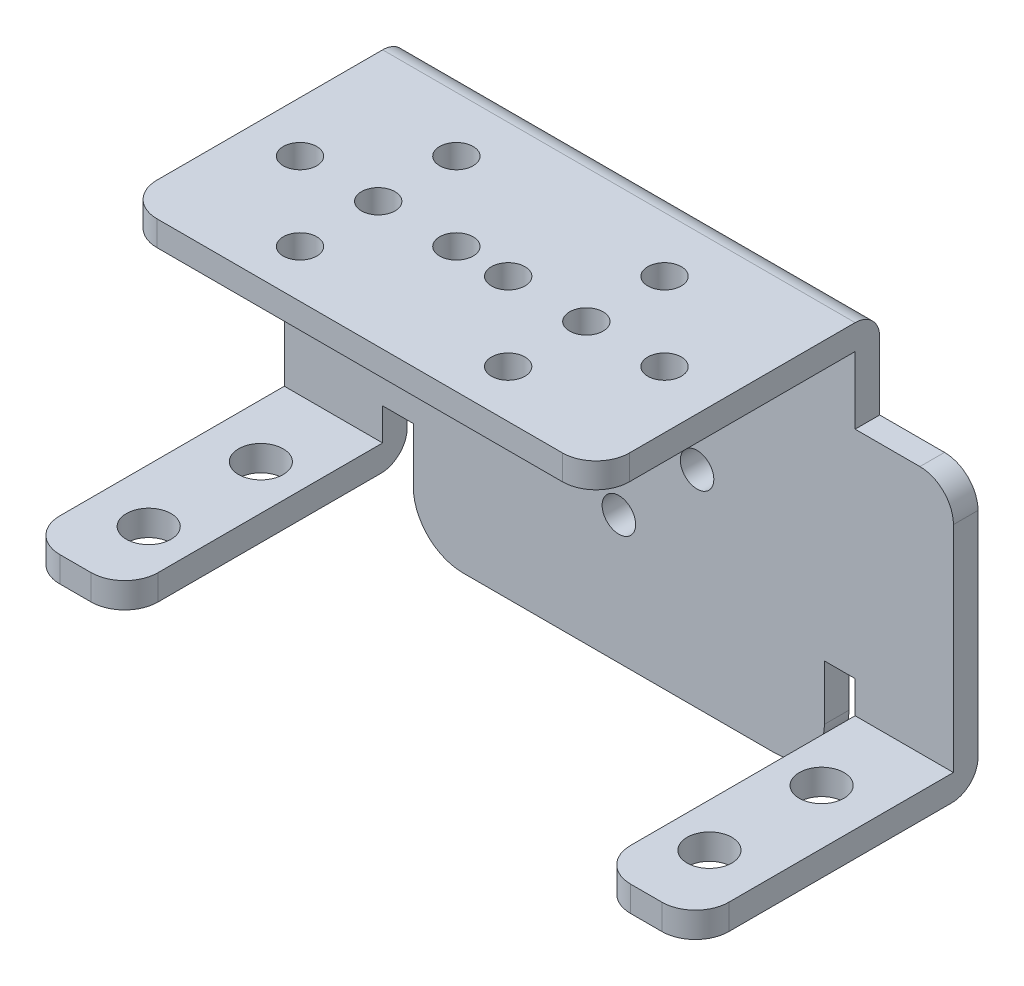
SolidWorks part; units mm, degrees
note: The reader was unsure of these and kept them because the rebuilt part matched: shared geometry of "Sketch1<3>", "Sketch1<4>".
ref_plane "前视基准面" through (0, 0, 0) normal (0, 0, 1) x (1, 0, 0)
ref_plane "上视基准面" through (0, 0, 0) normal (0, 1, 0) x (1, 0, 0)
ref_plane "右视基准面" through (0, 0, 0) normal (1, 0, 0) x (0, 0, -1)
sketch "Sketch1" plane through (0, 0, 0) normal (0, 0, 1) x (1, 0, 0)
  line L0 (-21.15, 16.24) -> (21.15, 16.24)
  line L1 (-21.15, 18.48) -> (21.15, 18.48)
  line L2 (-21.15, 18.48) -> (-21.15, -14.28)
  line L3 (-4.3498, -18.48) -> (13.96, -18.48)
  line L4 (21.15, 18.48) -> (21.15, -14.28)
  line L5 (-13.96, -18.48) -> (-4.3498, -18.48)
  line L6 (-18.4, -9.12) -> (18.4, -9.12)
  line L7 (-18.4, -9.12) -> (-18.4, -14.04)
  line L8 (-13.96, -18.48) -> (13.96, -18.48)
  line L9 (18.4, -9.12) -> (18.4, -14.04)
  line L10 (-4.3498, -18.48) -> (13.96, -18.48)
  line L11 (18.4, -9.12) -> (21.15, -9.12)
  line L12 (21.15, 10.22) -> (29.95, 10.22)
  line L13 (21.15, 10.22) -> (21.15, -14.28)
  line L14 (21.15, -14.28) -> (29.95, -14.28)
  line L15 (29.95, 10.22) -> (29.95, -14.28)
  line L16 (-29.95, 10.22) -> (-21.15, 10.22)
  line L17 (-29.95, 10.22) -> (-29.95, -14.28)
  line L18 (-29.95, -14.28) -> (-21.15, -14.28)
  line L19 (-21.15, 10.22) -> (-21.15, -14.28)
  line L20 (18.4, -9.12) -> (21.15, -9.12)
  line L21 (18.4, -9.12) -> (21.15, -9.12)
  line L22 (-18.4, -9.12) -> (-21.15, -9.12)
  line L24 (21.15, -12) -> (29.95, -12)
  line L25 (21.15, -12) -> (21.15, -14.28)
  line L26 (21.15, -14.28) -> (29.95, -14.28)
  line L27 (29.95, -12) -> (29.95, -14.28)
  line L28 (-29.95, -12) -> (-21.15, -12)
  line L29 (-29.95, -12) -> (-29.95, -14.28)
  line L30 (-29.95, -14.28) -> (-21.15, -14.28)
  line L31 (-21.15, -12) -> (-21.15, -14.28)
  arc A0 (-13.96, -18.48) -> (-18.4, -14.04) centre (-13.96, -14.04) cw
  arc A1 (13.96, -18.48) -> (18.4, -14.04) centre (13.96, -14.04) ccw
  point P20 (18.4, -18.48)
  point P30 (-25.55, -14.28)
  point P32 (-25.55, -12)
  dimension "D9" = 4.44
  dimension "D10" = 4.44
  dimension "D2" = 42.3
  dimension "D3" = 21.15
  dimension "D4" = 18.48
  dimension "D5" = 2.24
  dimension "D6" = 9.36
  dimension "D7" = 36.8
  dimension "D8" = 18.4
  dimension "D11" = 18.48
  dimension "D12" = 24.5
  dimension "D13" = 24.5
  dimension "D14" = 8.8
  dimension "D15" = 8.8
  dimension "D16" = 32.76
  dimension "D17" = 32.76
  dimension "D18" = 2.28
  dimension "D19" = 2.28
extrude "Boss-Extrude1" add sketch "Sketch1" along normal blind 2.2 contours L22 L6 L11 L4 L0 L2 | L3 A1 L9 L6 L7 A0 L5 | L17 L28 L19 L2 L16 | L4 L24 L15 L12
extrude "Boss-Extrude2" add sketch "Sketch1<3>" along normal blind 25.4 contours L4 L1 L2 L0
sketch "Sketch1<3>" plane through (0, 0, 0) normal (0, 0, 1) x (1, 0, 0) same geometry as "Sketch1"
extrude "Boss-Extrude3" add sketch "Sketch1<4>" along normal blind 25.3 contours L28 L17 L18 L2 | L24 L13 L14 L15
sketch "Sketch1<4>" plane through (0, 0, 0) normal (0, 0, 1) x (1, 0, 0) same geometry as "Sketch1"
fillet "Fillet13" radius 3 1 edges at (-21.15, -13.14, 25.3)
fillet "Fillet14" radius 3 1 edges at (-29.95, -13.14, 25.3)
fillet "Fillet15" radius 3 1 edges at (29.95, -13.14, 25.3)
fillet "Fillet16" radius 3 1 edges at (21.15, -13.14, 25.3)
fillet "Fillet18" radius 3 1 edges at (21.15, 17.36, 25.4)
fillet "Fillet19" radius 3 1 edges at (-21.15, 17.36, 25.4)
fillet "Fillet20" radius 3 1 edges at (29.95, 10.22, 1.1)
fillet "Fillet21" radius 3 1 edges at (-29.95, 10.22, 1.1)
sketch "Sketch2" plane through (0, -14.28, 0) normal (0, -1, 0) x (1, 0, 0)
  line L0 (24.15, 25.3) -> (26.95, 25.3) construction
  line L1 (25.05, 19.14) -> (25.05, 9.1) construction
  line L2 (21.15, 22.3) -> (21.15, 0) construction
  line L3 (-26.95, 25.3) -> (-24.15, 25.3) construction
  line L5 (-21.15, 22.3) -> (-21.15, 0) construction
  circle A0 centre (25.05, 19.14) radius 2
  circle A1 centre (25.05, 9.1) radius 2
  circle A2 centre (-25.15, 19.14) radius 2
  circle A3 centre (-25.15, 9.1) radius 2
  dimension "D1" = 4
  dimension "D2" = 4
  dimension "D7" = 4
  dimension "D8" = 4
  dimension "D3" = 6.16
  dimension "D4" = 10.04
  dimension "D5" = 3.9
  dimension "D9" = 6.16
  dimension "D10" = 4
  dimension "D11" = 10.04
fillet "Fillet24" radius 2.36 1 edges at (-25.55, -14.28, 0)
fillet "Fillet25" radius 2.36 1 edges at (25.55, -14.28, 0)
fillet "Fillet26" radius 2.2 1 edges at (0, 18.48, 0)
extrude "Cut-Extrude1" cut sketch "Sketch2" against normal blind 10
sketch "Sketch3" plane through (0, 18.48, 0) normal (0, 1, 0) x (1, 0, 0)
  line L0 (21.15, -2.2) -> (-21.15, -2.2) construction
  line L1 (-21.15, -22.4) -> (-21.15, -2.2) construction
  line L2 (-18.15, -25.4) -> (18.15, -25.4) construction
  line L3 (21.15, -22.4) -> (21.15, -2.2) construction
  circle A0 centre (9.03, -14.14) radius 1.5
  circle A1 centre (9.03, -7.14) radius 1.5
  circle A2 centre (16.03, -14.14) radius 1.5
  circle A3 centre (9.03, -21.14) radius 1.5
  circle A4 centre (2.03, -14.14) radius 1.5
  circle A5 centre (-9.6054, -14.14) radius 1.5
  circle A6 centre (-9.6054, -7.14) radius 1.5
  circle A7 centre (-2.6054, -14.14) radius 1.5
  circle A8 centre (-9.6054, -21.14) radius 1.5
  circle A9 centre (-16.6054, -14.14) radius 1.5
  point P0 (9.03, -14.14)
  point P3 (0, 0)
  point P15 (9.03, -14.14)
  point P31 (-9.6054, -14.14)
  dimension "D1" = 3
  dimension "D2" = 3
  dimension "D7" = 3
  dimension "D8" = 3
  dimension "D3" = 7
  dimension "D5" = 7
  dimension "D6" = 11.5446
  dimension "D10" = 4.94
  dimension "D11" = 23.2
  dimension "D12" = 42.3
  dimension "D13" = 12.12
  dimension "D4" = 4
  dimension "D9" = 4
extrude "Cut-Extrude2" cut sketch "Sketch3" against normal blind 10
sketch "Sketch4" plane through (0, 0, 0) normal (0, 0, -1) x (-1, 0, 0)
  line L0 (-21.15, -9.12) -> (-18.4, -9.12) construction
  line L1 (18.4, -9.12) -> (21.15, -9.12) construction
  line L2 (-21.15, -9.12) -> (-18.4, -9.12)
  line L3 (18.4, -9.12) -> (21.15, -9.12)
  line L4 (-21.15, 18.48) -> (21.15, 18.48) construction
  line L5 (-21.15, 18.48) -> (21.15, 18.48)
  circle A0 centre (0, 7) radius 1.5
  circle A1 centre (0, 0) radius 1.5
  circle A2 centre (0, -7) radius 1.5
  circle A3 centre (7, 0) radius 1.5
  circle A4 centre (-7, 0) radius 1.5
  dimension "D1" = 3
  dimension "D2" = 3
  dimension "D4" = 3
  dimension "D6" = 3
  dimension "D8" = 3
  dimension "D3" = 7
  dimension "D5" = 7
  dimension "D7" = 7
  dimension "D9" = 7
extrude "Cut-Extrude3" cut sketch "Sketch4" against normal blind 10 contours A4 | A0 | A3 | A2 | A1
